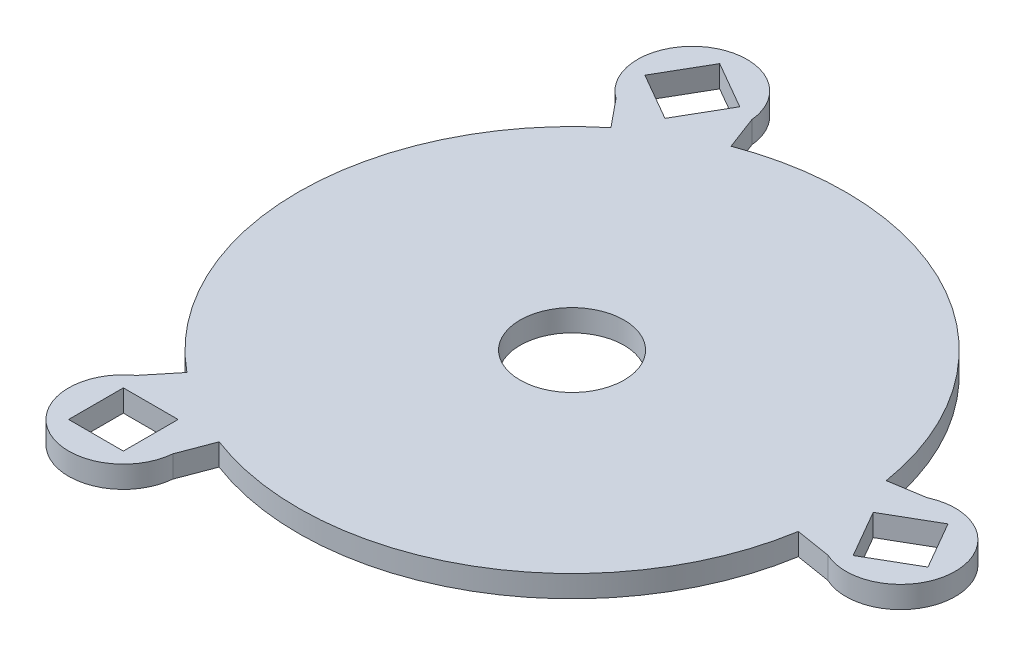
SolidWorks part; units mm, degrees
ref_plane "Front Plane" through (0, 0, 0) normal (0, 0, 1) x (1, 0, 0)
ref_plane "Top Plane" through (0, 0, 0) normal (0, 1, 0) x (1, 0, 0)
ref_plane "Right Plane" through (0, 0, 0) normal (1, 0, 0) x (0, 0, -1)
sketch "Sketch1" plane through (0, 0, 0) normal (0, 1, 0) x (1, 0, 0)
  line L0 (0, 0) -> (-15, -25.9808) construction
  line L4 (-17.5, -23.4808) -> (-12.5, -23.4808)
  line L5 (-17.5, -23.4808) -> (-17.5, -28.4808)
  line L6 (-17.5, -28.4808) -> (-12.5, -28.4808)
  line L7 (-12.5, -23.4808) -> (-12.5, -28.4808)
  line L8 (0, 0) -> (-17.8866, -21.8982)
  line L15 (0, 0) -> (-10.0211, -26.4394)
  line L16 (-11.5849, 26.8958) -> (-14.0849, 22.5657)
  line L17 (-11.5849, 26.8958) -> (-15.9151, 29.3958)
  line L18 (-15.9151, 29.3958) -> (-18.4151, 25.0657)
  line L19 (-14.0849, 22.5657) -> (-18.4151, 25.0657)
  line L20 (0, 0) -> (-10.0211, 26.4394)
  line L21 (0, 0) -> (-15, 25.9808) construction
  line L22 (0, 0) -> (-17.8866, 21.8982)
  line L23 (29.0849, -3.4151) -> (26.5849, 0.9151)
  line L24 (29.0849, -3.4151) -> (33.4151, -0.9151)
  line L25 (33.4151, -0.9151) -> (30.9151, 3.4151)
  line L26 (26.5849, 0.9151) -> (30.9151, 3.4151)
  line L27 (0, 0) -> (27.9077, -4.5412)
  line L28 (0, 0) -> (30, 0) construction
  line L29 (0, 0) -> (27.9077, 4.5412)
  line L30 (0, 0) -> (0, -25) construction
  circle A0 centre (0, 0) radius 25
  arc A1 (-17.8866, -21.8982) -> (-10.0211, -26.4394) centre (-15, -25.9808) ccw
  arc A2 (-10.0211, 26.4394) -> (-17.8866, 21.8982) centre (-15, 25.9808) ccw
  arc A3 (27.9077, -4.5412) -> (27.9077, 4.5412) centre (30, 0) ccw
  point P8 (-15, -28.4808)
  point P9 (-17.5, -25.9808)
  point P29 (0, 0)
  dimension "D1" = 50
  dimension "D5" = 5
  dimension "D2" = 30
  dimension "D3" = 5
  dimension "D4" = 28.2748
  dimension "D6" = 3
  dimension "D7" = 120
  dimension "D8" = 120
  dimension "D9" = 120
  dimension "D10" = 30
extrude "Boss-Extrude1" add sketch "Sketch1" along normal blind 2 contours L8 A1 L15 A0 L4 L7 L6 L5 | L27 A3 L29 A0 L23 L26 L25 L24 | L20 A2 L22 A0 L16 L19 L18 L17 | A0 region at (-12.5805, 0, 21.79) region at (-12.5805, 0, -21.79) region at (25.062, 0, 2.0257)
ref_plane "top_face" through (0, 0, 0) normal (0, -1, 0) x (-1, 0, 0)
sketch "Sketch2" plane through (0, 0, 0) normal (0, -1, 0) x (-1, 0, 0)
  circle A0 centre (0, 0) radius 4.75
  dimension "D1" = 9.5
extrude "Cut-Extrude1" cut sketch "Sketch2" against normal up to next
ref_axis "Axis1" through (0, 2, 0) along (0, -1, 0)
sketch "Sketch3" plane through (0, 0, 0) normal (0, -1, 0) x (-1, 0, 0)
  line L0 (17.5, 8) -> (-17.5, 8) construction
  circle A0 centre (17.5, 8) radius 1.9
  circle A1 centre (-17.5, 8) radius 1.9
  point P4 (0, 8)
  dimension "D1" = 3.8
  dimension "D2" = 35
  dimension "D3" = 8
extrude "Boss-Extrude2" add sketch "Sketch3" along normal blind 2
fillet "Fillet1" radius 0.5 2 edges at (17.5, -2, -9.9) (-17.5, -2, -9.9)
